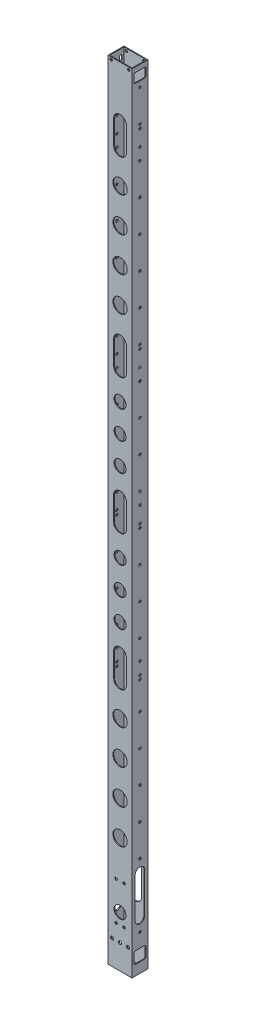
SolidWorks part; units mm, degrees
material "6061 合金"
ref_plane "Front" through (0, 0, 0) normal (0, 0, 1) x (1, 0, 0)
ref_plane "Top" through (0, 0, 0) normal (0, 1, 0) x (1, 0, 0)
ref_plane "Right" through (0, 0, 0) normal (1, 0, 0) x (0, 0, -1)
sketch "草图1" plane through (0, 0, 0) normal (0, 1, 0) x (1, 0, 0)
  line L1 (-15, -10) -> (15, -10)
  line L2 (-15, -10) -> (-15, 10)
  line L3 (-15, 10) -> (15, 10)
  line L4 (15, -10) -> (15, 10)
  line L5 (-15, -10) -> (15, 10) construction
  line L6 (-15, 10) -> (15, -10) construction
  line L7 (-14, -9) -> (14, -9)
  line L8 (-14, -9) -> (-14, 9)
  line L9 (-14, 9) -> (14, 9)
  line L10 (14, -9) -> (14, 9)
  line L11 (-14, -9) -> (14, 9) construction
  line L12 (-14, 9) -> (14, -9) construction
  point P0 (0, 0)
  point P5 (0, 0)
  dimension "D1" = 20
  dimension "D2" = 30
  dimension "D3" = 1
  dimension "D4" = 1
extrude "凸台-拉伸1" add sketch "草图1" along normal blind 980
sketch "草图3" plane through (15, 0, 0) normal (1, 0, 0) x (0, 0, -1)
  line L0 (0, 310) -> (0, 330) construction
  line L1 (0, 0) -> (0, 50000) construction
  line L2 (0, 910) -> (0, 890) construction
  line L4 (-10, 980) -> (10, 980) construction
  line L5 (-10, 490) -> (10, 490) construction
  line L6 (-10, 980) -> (-10, 0) construction
  line L7 (10, 980) -> (10, 0) construction
  line L8 (0, 500) -> (0, 480) construction
  line L9 (0, 670) -> (0, 650) construction
  line L10 (0, 70) -> (0, 90) construction
  circle A4 centre (0, 890) radius 1.5
  circle A5 centre (0, 910) radius 1.5
  circle A10 centre (0, 500) radius 1.5
  circle A11 centre (0, 480) radius 1.5
  circle A12 centre (0, 670) radius 1.5
  circle A13 centre (0, 650) radius 1.5
  circle A14 centre (0, 330) radius 1.5
  circle A15 centre (0, 310) radius 1.5
  circle A16 centre (0, 70) radius 1.5
  circle A17 centre (0, 90) radius 1.5
  dimension "D6" = 3
  dimension "D8" = 3
  dimension "D9" = 3
  dimension "D12" = 70
  dimension "D15" = 20
  dimension "D16" = 3
  dimension "D7" = 3
  dimension "D11" = 10
  dimension "D14" = 3
  dimension "D10" = 20
  dimension "D13" = 20
  dimension "D17" = 220
extrude "切除-拉伸2" cut sketch "草图3" against normal through all
sketch "草图4" plane through (15, 0, 0) normal (1, 0, 0) x (0, 0, -1)
  line L0 (0, 0) -> (0, 50000) construction
  line L1 (-10, 0) -> (10, 0) construction
  line L2 (-10, 980) -> (10, 980) construction
  line L3 (5, 968) -> (5, 972) construction
  line L4 (3.4, 968) -> (3.4, 972)
  line L5 (6.6, 968) -> (6.6, 972)
  line L6 (-5, 968) -> (-5, 972) construction
  line L7 (-3.4, 968) -> (-3.4, 972)
  line L8 (-6.6, 968) -> (-6.6, 972)
  circle A0 centre (-5, 10) radius 1.6 construction
  circle A1 centre (5, 10) radius 1.6 construction
  circle A2 centre (-5, 970) radius 1.6 construction
  circle A3 centre (5, 970) radius 1.6 construction
  arc A4 (3.4, 968) -> (6.6, 968) centre (5, 968) ccw
  arc A5 (6.6, 972) -> (3.4, 972) centre (5, 972) ccw
  arc A6 (-3.4, 968) -> (-6.6, 968) centre (-5, 968) cw
  arc A7 (-6.6, 972) -> (-3.4, 972) centre (-5, 972) cw
  point P17 (5, 970)
  point P24 (-5, 970)
  dimension "D1" = 3.2
  dimension "D4" = 3.2
  dimension "D7" = 1.6
  dimension "D2" = 10
  dimension "D3" = 10
  dimension "D5" = 10
  dimension "D6" = 10
  dimension "D8" = 4
extrude "切除-拉伸3" cut sketch "草图4" against normal through all
sketch "草图5" plane through (15, 0, 0) normal (1, 0, 0) x (0, 0, -1)
  line L0 (0, 0) -> (0, 50000) construction
  line L1 (10, 968) -> (-10, 968) construction
  line L2 (10, 980) -> (10, 0) construction
  line L3 (-10, 980) -> (-10, 0) construction
  line L4 (-10, 980) -> (10, 980) construction
  line L6 (-7.5, 974) -> (7.5, 974)
  line L7 (-7.5, 974) -> (-7.5, 962)
  line L8 (-7.5, 962) -> (7.5, 962)
  line L9 (7.5, 974) -> (7.5, 962)
  line L10 (-7.5, 974) -> (7.5, 962) construction
  line L11 (-7.5, 962) -> (7.5, 974) construction
  point P13 (0, 968)
  dimension "D1" = 12
  dimension "D2" = 12
  dimension "D3" = 15
extrude "切除-拉伸4" cut sketch "草图5" against normal blind 10
sketch "草图6" plane through (0, 0, -10) normal (0, 0, -1) x (-1, 0, 0)
  line L0 (-15, 91.5) -> (-15, 88.5) construction
  line L1 (-15, 71.5) -> (-15, 68.5) construction
  line L2 (-15, 91.5) -> (-15, 88.5) construction
  line L3 (-15, 71.5) -> (-15, 68.5) construction
  line L4 (-15, 891.5) -> (-15, 888.5) construction
  line L5 (-15, 911.5) -> (-15, 908.5) construction
  line L6 (-15, 671.5) -> (-15, 668.5) construction
  line L7 (-15, 651.5) -> (-15, 648.5) construction
  line L8 (-15, 501.5) -> (-15, 498.5) construction
  line L9 (-15, 481.5) -> (-15, 478.5) construction
  line L10 (-15, 331.5) -> (-15, 328.5) construction
  line L11 (-15, 311.5) -> (-15, 308.5) construction
  line L12 (-15, 891.5) -> (-15, 888.5) construction
  line L13 (-15, 911.5) -> (-15, 908.5) construction
  line L14 (-15, 671.5) -> (-15, 668.5) construction
  line L15 (-15, 651.5) -> (-15, 648.5) construction
  line L16 (-15, 501.5) -> (-15, 498.5) construction
  line L17 (-15, 481.5) -> (-15, 478.5) construction
  line L18 (-15, 331.5) -> (-15, 328.5) construction
  line L19 (-15, 311.5) -> (-15, 308.5) construction
  line L20 (0, 65) -> (0, 95) construction
  line L21 (-8, 65) -> (-8, 95)
  line L22 (8, 65) -> (8, 95)
  line L23 (0, 475) -> (0, 505) construction
  line L24 (-15, 88.5) -> (-15, 71.5) construction
  line L25 (-15, 80) -> (-40.807, 80) construction
  line L26 (0, 305) -> (0, 335) construction
  line L27 (-8, 305) -> (-8, 335)
  line L28 (8, 305) -> (8, 335)
  line L29 (0, 65) -> (0, 305) construction
  line L30 (-8, 475) -> (-8, 505)
  line L31 (8, 475) -> (8, 505)
  line L32 (0, 645) -> (0, 675) construction
  line L33 (-8, 645) -> (-8, 675)
  line L34 (8, 645) -> (8, 675)
  line L35 (0, 305) -> (0, 475) construction
  line L36 (0, 885) -> (0, 915) construction
  line L37 (-8, 885) -> (-8, 915)
  line L38 (8, 885) -> (8, 915)
  line L39 (0, 645) -> (0, 885) construction
  line L40 (0, 490) -> (-90.401, 490) construction
  arc A0 (-8, 65) -> (8, 65) centre (0, 65) ccw
  arc A1 (8, 95) -> (-8, 95) centre (0, 95) ccw
  arc A2 (-8, 305) -> (8, 305) centre (0, 305) ccw
  arc A3 (8, 335) -> (-8, 335) centre (0, 335) ccw
  arc A4 (-8, 475) -> (8, 475) centre (0, 475) ccw
  arc A5 (8, 505) -> (-8, 505) centre (0, 505) ccw
  arc A6 (-8, 645) -> (8, 645) centre (0, 645) ccw
  arc A7 (8, 675) -> (-8, 675) centre (0, 675) ccw
  arc A8 (-8, 885) -> (8, 885) centre (0, 885) ccw
  arc A9 (8, 915) -> (-8, 915) centre (0, 915) ccw
  circle A10 centre (0, 135) radius 9
  circle A11 centre (0, 178.3333) radius 9
  circle A12 centre (0, 221.6667) radius 9
  circle A13 centre (0, 265) radius 9
  circle A14 centre (0, 845) radius 9
  circle A16 centre (0, 801.6667) radius 9
  circle A17 centre (0, 758.3333) radius 9
  circle A18 centre (0, 715) radius 9
  circle A19 centre (0, 440) radius 7.5
  circle A20 centre (0, 405) radius 7.5
  circle A21 centre (0, 370) radius 7.5
  circle A22 centre (0, 610) radius 7.5
  circle A23 centre (0, 575) radius 7.5
  circle A24 centre (0, 540) radius 7.5
  point P23 (0, 80)
  point P34 (0, 320)
  point P42 (0, 490)
  point P49 (0, 660)
  point P58 (0, 900)
  dimension "D1" = 8
  dimension "D10" = 18
  dimension "D11" = 40
  dimension "D12" = 40
  dimension "D13" = 43.3333
  dimension "D14" = 40
  dimension "D16" = 40
  dimension "D18" = 35
  dimension "D19" = 35
  dimension "D20" = 35
  dimension "D21" = 15
  dimension "D2" = 30
  dimension "D3" = 2
  dimension "D4" = 240
  dimension "D5" = 3
  dimension "D6" = 170
  dimension "D8" = 240
  dimension "D9" = 4
  dimension "D7" = 2
  dimension "D15" = 4
  dimension "D17" = 3
extrude "切除-拉伸5" cut sketch "草图6" against normal through all
sketch "草图7" plane through (15, 0, 0) normal (1, 0, 0) x (0, 0, -1)
  line L1 (-10, 980) -> (-10, 0) construction
  line L2 (-10, 0) -> (10, 0) construction
  line L3 (0, 0) -> (0, 24.669) construction
  line L4 (-10, 980) -> (10, 980) construction
  circle A0 centre (-5, 5) radius 1.5
  circle A1 centre (5, 5) radius 1.5
  circle A2 centre (-5, 975) radius 1.5
  circle A3 centre (5, 975) radius 1.5
  dimension "D1" = 5
  dimension "D2" = 5
  dimension "D3" = 3
  dimension "D4" = 5
  dimension "D5" = 5
  dimension "D6" = 3
extrude "切除-拉伸6" [suppressed] cut sketch "草图7" against normal through all
sketch "草图9" plane through (0, 0, 10) normal (0, 0, 1) x (1, 0, 0)
  line L0 (15, 980) -> (15, 0) construction
  line L1 (-15, 0) -> (15, 0) construction
  line L2 (0, 0) -> (0, 1062.0992) construction
  line L3 (-15, 980) -> (15, 980) construction
  circle A0 centre (11, 3) radius 1.5 construction
  circle A1 centre (11, 977) radius 1.5
  circle A2 centre (-11, 3) radius 1.5 construction
  circle A3 centre (-11, 977) radius 1.5
  dimension "D3" = 3
  dimension "D4" = 4
  dimension "D5" = 3
  dimension "D1" = 4
  dimension "D2" = 3
extrude "切除-拉伸7" cut sketch "草图9" against normal through all
sketch "草图13" plane through (0, 0, 0) normal (0, -1, 0) x (1, 0, 0)
  line L4 (15, -10) -> (15, 10)
  line L5 (15, 10) -> (-15, 10)
  line L6 (-15, 10) -> (-15, -10)
  line L7 (-15, -10) -> (15, -10)
  line L8 (15, -10) -> (15, 10)
  line L9 (15, 10) -> (-15, 10)
  line L10 (-15, 10) -> (-15, -10)
  line L11 (-15, -10) -> (15, -10)
  line L12 (14, 9) -> (-14, 9)
  line L13 (14, -9) -> (14, 9)
  line L14 (-14, -9) -> (14, -9)
  line L15 (-14, 9) -> (-14, -9)
  line L16 (14, 9) -> (-14, 9)
  line L17 (14, -9) -> (14, 9)
  line L18 (-14, -9) -> (14, -9)
  line L19 (-14, 9) -> (-14, -9)
  dimension "D1" = 0
  dimension "D2" = 0
extrude "凸台-拉伸2" add sketch "草图13" along normal blind 10
sketch "草图11" plane through (-14, 0, 0) normal (1, 0, 0) x (0, 0, -1)
  line L0 (0, 0) -> (0, 111.3677) construction
  line L1 (-5, 5) -> (-5, 15) construction
  line L2 (-6.6, 5) -> (-6.6, 15)
  line L3 (-3.4, 5) -> (-3.4, 15)
  line L4 (5, 5) -> (5, 15) construction
  line L5 (6.6, 5) -> (6.6, 15)
  line L6 (3.4, 5) -> (3.4, 15)
  line L8 (10, -10) -> (-10, -10) construction
  arc A0 (-6.6, 5) -> (-3.4, 5) centre (-5, 5) ccw
  arc A1 (-3.4, 15) -> (-6.6, 15) centre (-5, 15) ccw
  arc A2 (6.6, 5) -> (3.4, 5) centre (5, 5) cw
  arc A3 (3.4, 15) -> (6.6, 15) centre (5, 15) cw
  point P5 (-5, 10)
  point P12 (5, 10)
  dimension "D4" = 1.6
  dimension "D1" = 10
  dimension "D2" = 20
  dimension "D3" = 10
extrude "切除-拉伸8" cut sketch "草图11" against normal blind 60
sketch "草图15" plane through (15, 0, 0) normal (1, 0, 0) x (0, 0, -1)
  line L0 (0, -10) -> (0, 26.437) construction
  line L1 (10, -10) -> (-10, -10) construction
  line L3 (-7.5, 17.5) -> (7.5, 17.5)
  line L4 (-7.5, 17.5) -> (-7.5, 2.5)
  line L5 (-7.5, 2.5) -> (7.5, 2.5)
  line L6 (7.5, 17.5) -> (7.5, 2.5)
  line L7 (-7.5, 17.5) -> (7.5, 2.5) construction
  line L8 (-7.5, 2.5) -> (7.5, 17.5) construction
  point P5 (0, 10)
  dimension "D1" = 20
  dimension "D2" = 15
  dimension "D3" = 15
extrude "切除-拉伸10" cut sketch "草图15" against normal blind 5
fillet "圆角1" radius 2 4 edges at (14.5, 2.5, -7.5) (14.5, 2.5, 7.5) (14.5, 17.5, -7.5) (14.5, 17.5, 7.5)
sketch "草图16" plane through (0, 0, 10) normal (0, 0, 1) x (1, 0, 0)
  line L0 (0, -10) -> (0, 90.7842) construction
  line L1 (15, -10) -> (-15, -10) construction
  circle A0 centre (10, 21) radius 2
  circle A1 centre (0, 21) radius 2
  circle A2 centre (-10, 21) radius 2
  dimension "D1" = 31
  dimension "D2" = 4
  dimension "D3" = 20
extrude "切除-拉伸11" cut sketch "草图16" against normal blind 90
fillet "圆角2" radius 2 4 edges at (14.5, 962, -7.5) (14.5, 962, 7.5) (14.5, 974, 7.5) (14.5, 974, -7.5)
sketch "草图17" plane through (15, 0, 0) normal (1, 0, 0) x (0, 0, -1)
  line L0 (-10, 980) -> (10, 980) construction
  circle A0 centre (0, 955) radius 1.5
  circle A1 centre (0, 915) radius 1.5
  circle A2 centre (0, 875) radius 1.5
  circle A3 centre (0, 835) radius 1.5
  circle A4 centre (0, 795) radius 1.5
  circle A5 centre (0, 755) radius 1.5
  circle A6 centre (0, 715) radius 1.5
  circle A7 centre (0, 675) radius 1.5
  circle A8 centre (0, 635) radius 1.5
  circle A9 centre (0, 595) radius 1.5
  circle A10 centre (0, 555) radius 1.5
  circle A11 centre (0, 515) radius 1.5
  circle A12 centre (0, 475) radius 1.5
  circle A13 centre (0, 435) radius 1.5
  circle A14 centre (0, 395) radius 1.5
  circle A15 centre (0, 355) radius 1.5
  circle A16 centre (0, 315) radius 1.5
  circle A17 centre (0, 275) radius 1.5
  circle A18 centre (0, 235) radius 1.5
  circle A19 centre (0, 195) radius 1.5
  circle A20 centre (0, 155) radius 1.5
  circle A21 centre (0, 115) radius 1.5
  circle A22 centre (0, 75) radius 1.5
  circle A23 centre (0, 35) radius 1.5
  dimension "D1" = 3
  dimension "D3" = 25
  dimension "D2" = 24
extrude "切除-拉伸12" cut sketch "草图17" against normal blind 40
sketch "草图20" plane through (15, 0, 0) normal (1, 0, 0) x (0, 0, -1)
  line L0 (0, 0) -> (0, 121.9481) construction
  line L1 (0, 50) -> (0, 100) construction
  line L2 (-6, 50) -> (-6, 100)
  line L3 (6, 50) -> (6, 100)
  line L4 (10, -10) -> (-10, -10) construction
  arc A0 (-6, 50) -> (6, 50) centre (0, 50) ccw
  arc A1 (6, 100) -> (-6, 100) centre (0, 100) ccw
  point P5 (0, 75)
  dimension "D2" = 6
  dimension "D3" = 60
  dimension "D1" = 50
extrude "切除-拉伸15" cut sketch "草图20" against normal blind 51
sketch "草图21" plane through (0, 0, 10) normal (0, 0, 1) x (1, 0, 0)
  line L1 (-11.7833, 108.871) -> (10.404, 108.871)
  line L2 (-11.7833, 108.871) -> (-11.7833, 43.5326)
  line L3 (-11.7833, 43.5326) -> (10.404, 43.5326)
  line L4 (10.404, 108.871) -> (10.404, 43.5326)
extrude "凸台-拉伸3" add sketch "草图21" against normal blind 1
sketch "草图22" plane through (0, 0, 10) normal (0, 0, 1) x (1, 0, 0)
  line L0 (0, 92.5342) -> (0, -20.6994) construction
  line L1 (15, -10) -> (-15, -10) construction
  circle A0 centre (5, 40) radius 1.65
  circle A1 centre (-5, 40) radius 1.65
  circle A2 centre (5, 88) radius 1.65
  circle A3 centre (-5, 88) radius 1.65
  dimension "D1" = 3.3
  dimension "D4" = 10
  dimension "D5" = 48
  dimension "D6" = 5
  dimension "D7" = 50
  dimension "D2" = 2
  dimension "D3" = 2
extrude "切除-拉伸16" cut sketch "草图22" against normal blind 1
sketch "草图23" plane through (0, 0, 10) normal (0, 0, 1) x (1, 0, 0)
  circle A0 centre (0, 54.25) radius 7.5
  circle A1 centre (5, 40) radius 1.65 construction
  dimension "D1" = 15
  dimension "D2" = 14.25
extrude "切除-拉伸17" cut sketch "草图23" against normal blind 10
